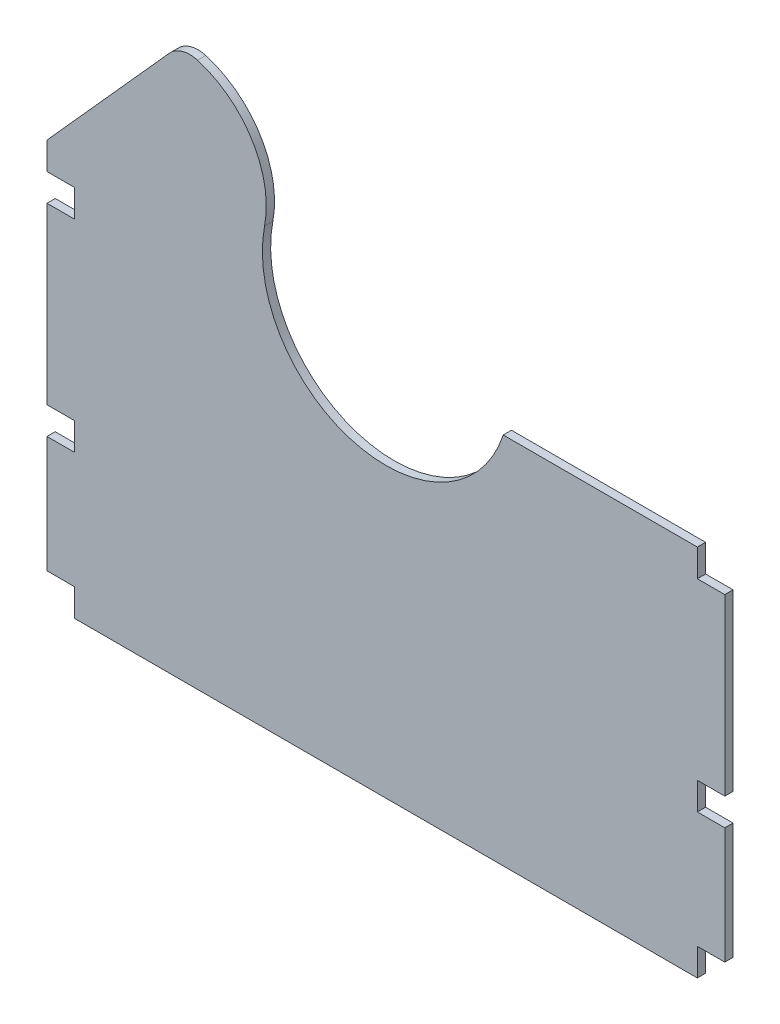
SolidWorks part; units mm, degrees
ref_plane "Plan de face" through (0, 0, 0) normal (0, 0, 1) x (1, 0, 0)
ref_plane "Plan de dessus" through (0, 0, 0) normal (0, 1, 0) x (1, 0, 0)
ref_plane "Plan de droite" through (0, 0, 0) normal (1, 0, 0) x (0, 0, -1)
sketch "Esquisse1" plane through (0, 0, 0) normal (0, 0, 1) x (1, 0, 0)
  line L0 (0, 0) -> (280.2, 0) construction
  line L1 (280.2, 0) -> (280.2, 127.45) construction
  line L2 (280.2, 127.45) -> (215.1, 200) construction
  line L3 (215.1, 200) -> (65.1, 200) construction
  line L4 (65.1, 200) -> (0, 127.45) construction
  line L5 (0, 0) -> (0, 127.45) construction
  line L6 (0, 0) -> (0, 127.45)
  line L7 (0, 127.45) -> (65.1, 200)
  line L8 (65.1, 200) -> (215.1, 200)
  line L9 (215.1, 200) -> (280.2, 127.45)
  line L10 (280.2, 127.45) -> (280.2, 0)
  line L11 (280.2, 0) -> (0, 0)
  point P3 (140.1, 200)
  point P8 (140.1, 0)
  dimension "D1" = 280.2
  dimension "D2" = 200
  dimension "D3" = 127.45
  dimension "D4" = 127.45
  dimension "D5" = 150
extrude "Boss.-Extru.1" add sketch "Esquisse1" along normal blind 3
sketch "Esquisse2" plane through (0, 0, 0) normal (0, 0, -1) x (-1, 0, 0)
  line L1 (-16.6, 252) -> (-16.6, 0) construction
  line L2 (-16.6, 0) -> (-16.6, 145.9694)
  line L3 (-16.6, 0) -> (0, 0)
  line L4 (0, 0) -> (0, 127.45)
  line L5 (0, 127.45) -> (-16.6, 145.9694)
  line L6 (-140.1, 200) -> (-140.1, -18.7191) construction
  line L7 (-215.1, 200) -> (-65.1, 200) construction
  line L8 (-280.2, 127.45) -> (-263.6, 145.9694)
  line L9 (-280.2, 0) -> (-280.2, 127.45)
  line L10 (-263.6, 0) -> (-280.2, 0)
  line L11 (-263.6, 0) -> (-263.6, 145.9694)
extrude "Enlèv. mat.-Extru.1" cut sketch "Esquisse2" against normal through all
sketch "Esquisse4" plane through (0, 0, 3) normal (0, 0, 1) x (1, 0, 0)
  line L0 (140.1, 200) -> (140.1, -14.9568) construction
  line L1 (215.1, 200) -> (65.1, 200) construction
  line L2 (16.6, 145.9497) -> (16.6, 0) construction
  line L3 (16.6, 0) -> (26.6, 0)
  line L4 (16.6, 0) -> (16.6, 10)
  line L5 (16.6, 10) -> (26.6, 10)
  line L6 (26.6, 0) -> (26.6, 10)
  line L7 (16.6, 52.4) -> (26.6, 52.4)
  line L8 (16.6, 52.4) -> (16.6, 62.4)
  line L9 (16.6, 62.4) -> (26.6, 62.4)
  line L10 (26.6, 52.4) -> (26.6, 62.4)
  line L11 (253.6, 126) -> (253.6, 136)
  line L12 (16.6, 126) -> (26.6, 126)
  line L13 (16.6, 126) -> (16.6, 136)
  line L14 (16.6, 136) -> (26.6, 136)
  line L15 (26.6, 126) -> (26.6, 136)
  line L16 (263.6, 136) -> (253.6, 136)
  line L17 (263.6, 126) -> (263.6, 136)
  line L18 (263.6, 126) -> (253.6, 126)
  line L19 (253.6, 52.4) -> (253.6, 62.4)
  line L20 (263.6, 62.4) -> (253.6, 62.4)
  line L21 (263.6, 52.4) -> (263.6, 62.4)
  line L22 (263.6, 52.4) -> (253.6, 52.4)
  line L23 (253.6, 0) -> (253.6, 10)
  line L24 (263.6, 10) -> (253.6, 10)
  line L25 (263.6, 0) -> (263.6, 10)
  line L26 (263.6, 0) -> (253.6, 0)
  point P19 (21.6, 62.4)
  dimension "D1" = 10
  dimension "D2" = 10
  dimension "D3" = 10
  dimension "D4" = 10
  dimension "D5" = 10
  dimension "D6" = 10
  dimension "D7" = 42.4
  dimension "D8" = 63.6
extrude "Enlèv. mat.-Extru.2" cut sketch "Esquisse4" against normal through all
sketch "Esquisse5" plane through (0, 0, 3) normal (0, 0, 1) x (1, 0, 0)
  line L0 (218.6812, 200) -> (140.1, 200)
  line L1 (215.1, 200) -> (65.1, 200) construction
  line L2 (140.1, 200) -> (140.1, 150) construction
  line L3 (61.5188, 200) -> (218.6812, 200)
  arc A0 (95.8981, 158.4375) -> (184.3019, 158.4375) centre (140.1, 150) ccw
  arc A1 (95.8981, 158.4375) -> (61.5188, 200) centre (61.5188, 165) ccw
  arc A2 (184.3019, 158.4375) -> (218.6812, 200) centre (218.6812, 165) cw
  point P7 (140.1, 200)
  line M26 (215.1, 200) -> (65.1, 200)
  dimension "D1" = 90
  dimension "D3" = 70
  dimension "D2" = 50
extrude "Enlèv. mat.-Extru.3" cut sketch "Esquisse5" against normal through all contours A0 A2 A1 M26 region at (140.1, 158.7154, 3)
fillet "Congé2" radius 10 2 edges at (64.9488, 199.8315, 1.5) (215.2512, 199.8315, 1.5)
sketch "Esquisse6" plane through (0, 0, 3) normal (0, 0, 1) x (1, 0, 0)
  line L0 (253.6, 136) -> (162.0371, 136)
  line L1 (162.0371, 136) -> (157.83, 194.7443)
  line L2 (157.83, 194.7443) -> (193.5906, 207.0651)
  line L3 (193.5906, 207.0651) -> (241.071, 207.0651)
  line L4 (241.071, 207.0651) -> (283.1422, 167.6985)
  line L5 (283.1422, 167.6985) -> (280.7381, 136)
  line L6 (280.7381, 136) -> (273.475, 135.4798)
  line L7 (273.475, 135.4798) -> (253.6, 136)
extrude "Enlèv. mat.-Extru.4" cut sketch "Esquisse6" against normal through all
